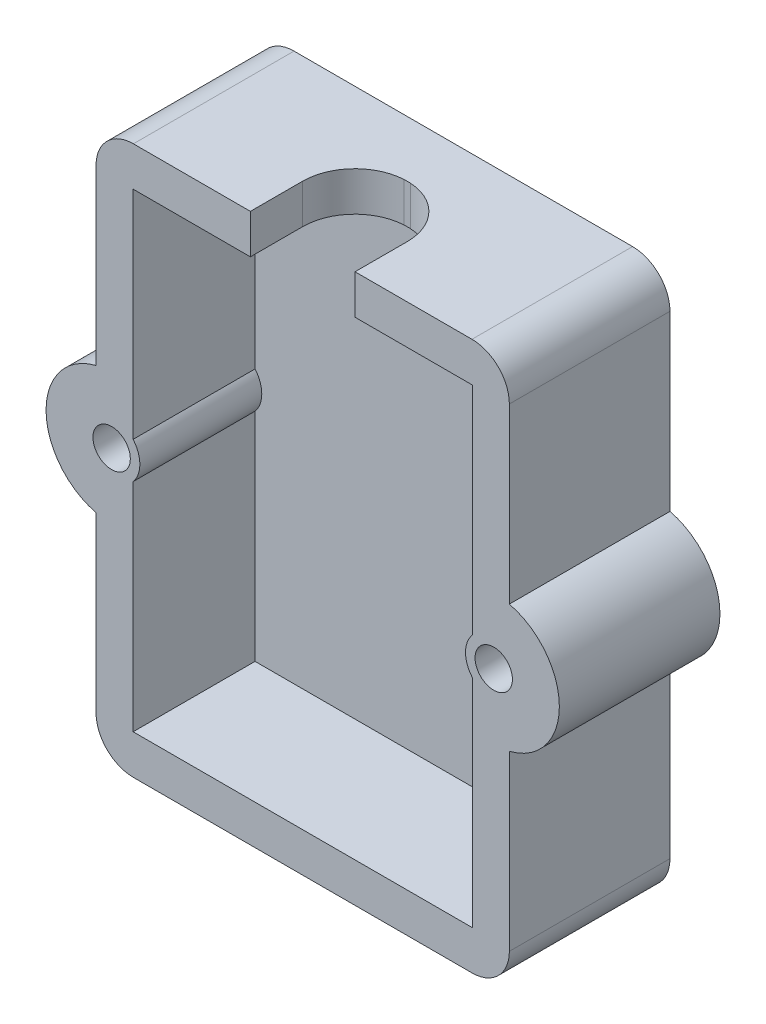
SolidWorks part; units mm, degrees
ref_plane "Front Plane" through (0, 0, 0) normal (0, 0, 1) x (1, 0, 0)
ref_plane "Top Plane" through (0, 0, 0) normal (0, 1, 0) x (1, 0, 0)
ref_plane "Right Plane" through (0, 0, 0) normal (1, 0, 0) x (0, 0, -1)
sketch "Sketch1" plane through (0, 0, 0) normal (0, 0, 1) x (1, 0, 0)
  line L0 (0, 0) -> (0, 25.5) construction
  line L1 (-15.5, 25.5) -> (15.5, 25.5) construction
  line L2 (-10.225, 12.45) -> (0, 12.45) construction
  line L3 (0, 12.45) -> (10.225, 12.45) construction
  line L4 (-11.06, -0.2336) -> (-11.06, 9.0408)
  line L9 (0, 25.1336) -> (0, -0.2336) construction
  line L10 (-9.06, 12.45) -> (9.06, 12.45) construction
  line L11 (-9.06, 27.1336) -> (9.06, 27.1336)
  line L12 (11.06, -0.2336) -> (11.06, 9.0408)
  line L13 (-9.06, -2.2336) -> (9.06, -2.2336)
  line L18 (-11.06, 15.8592) -> (-11.06, 25.1336)
  line L20 (11.06, 15.8592) -> (11.06, 25.1336)
  arc A2 (11.06, 15.8592) -> (11.06, 9.0408) centre (10.225, 12.45) cw
  arc A3 (-11.06, 15.8592) -> (-11.06, 9.0408) centre (-10.225, 12.45) ccw
  arc A4 (-11.06, -0.2336) -> (-9.06, -2.2336) centre (-9.06, -0.2336) ccw
  arc A5 (11.06, -0.2336) -> (9.06, -2.2336) centre (9.06, -0.2336) cw
  arc A6 (9.06, 27.1336) -> (11.06, 25.1336) centre (9.06, 25.1336) cw
  arc A8 (-11.06, 25.1336) -> (-9.06, 27.1336) centre (-9.06, 25.1336) cw
  dimension "D1" = 2
extrude "Boss-Extrude2" add sketch "Sketch1" along normal blind 8.595 contours L11 A6 L20 A2 L12 A5 L13 A4 L4 A3 L18 A8
sketch "Sketch2" plane through (0, 0, 8.595) normal (0, 0, 1) x (1, 0, 0)
  line L6 (0, -2.2336) -> (0, 27.1336) construction
  line L7 (-9.06, -2.2336) -> (9.06, -2.2336) construction
  line L8 (-9.06, 27.1336) -> (9.06, 27.1336) construction
  line L9 (13.735, 12.45) -> (-13.735, 12.45) construction
  line L10 (0, -0.2133) -> (0, 25.2203) construction
  line L11 (-10.5637, 12.45) -> (9.8863, 12.45) construction
  line L12 (-9.075, 13.4286) -> (-9.075, 25.025)
  line L13 (-9.075, -0.125) -> (9.075, -0.125)
  line L14 (-9.075, -0.125) -> (-9.075, 11.4714)
  line L15 (-9.075, 25.025) -> (9.075, 25.025)
  line L16 (9.075, -0.125) -> (9.075, 11.4714)
  line L17 (0, 25.025) -> (0, -0.125) construction
  line L18 (-9.075, 12.45) -> (9.075, 12.45) construction
  line L19 (9.075, 13.4286) -> (9.075, 25.025)
  arc A2 (11.06, 9.0408) -> (11.06, 15.8592) centre (10.225, 12.45) ccw construction
  arc A3 (-11.06, 15.8592) -> (-11.06, 9.0408) centre (-10.225, 12.45) ccw construction
  arc A4 (-9.075, 11.4714) -> (-9.075, 13.4286) centre (-10.225, 12.45) ccw
  arc A5 (9.075, 11.4714) -> (9.075, 13.4286) centre (10.225, 12.45) cw
  point P6 (0, 12.45)
  dimension "D1" = 25.15
  dimension "D2" = 18.15
sketch "Sketch5" plane through (0, 0, 8.595) normal (0, 0, 1) x (1, 0, 0)
  line L0 (0, 27.1336) -> (0, -2.2336) construction
  line L1 (-10.225, 12.45) -> (10.315, 12.45) construction
  line L3 (13.735, 12.45) -> (-13.735, 12.45) construction
  circle A0 centre (-10.225, 12.45) radius 1
  circle A1 centre (10.225, 12.45) radius 1
extrude "Cut-Extrude3" cut sketch "Sketch5" against normal up to next
extrude "Cut-Extrude4" cut sketch "Sketch2" against normal blind 6.525
sketch "Sketch3" plane through (0, 27.1336, 0) normal (0, 1, 0) x (1, 0, 0)
  line L0 (0, 0) -> (0, -8.595) construction
  line L1 (-9.06, -8.595) -> (9.06, -8.595) construction
  line L2 (11.06, -4.2975) -> (-11.06, -4.2975) construction
  line L3 (11.06, -8.595) -> (11.06, 0) construction
  line L4 (-11.06, -8.595) -> (-11.06, 0) construction
  line L5 (-9.06, 0) -> (9.06, 0) construction
  line L7 (-0.1673, -3.005) -> (0.1673, -3.005)
  line L8 (-2.8, -5.8) -> (-2.8, -8.595)
  line L9 (-2.8, -8.595) -> (2.8, -8.595)
  line L10 (2.8, -5.8) -> (2.8, -8.595)
  line L11 (0, -8.595) -> (0, -3.005) construction
  line L12 (-2.8, -5.8) -> (2.8, -5.8) construction
  arc A0 (2.8, -5.8) -> (-2.8, -5.8) centre (0, -5.8) ccw
  arc A1 (-0.1673, -8.595) -> (0.1673, -8.595) centre (0, -5.8) ccw
  line M4 (-9.06, -8.595) -> (9.06, -8.595)
  dimension "D1" = 5.8
extrude "Cut-Extrude2" cut sketch "Sketch3" against normal up to next contours L10 A0 L7 L8 L9 M4 region at (0, 27.1336, 6.059)
